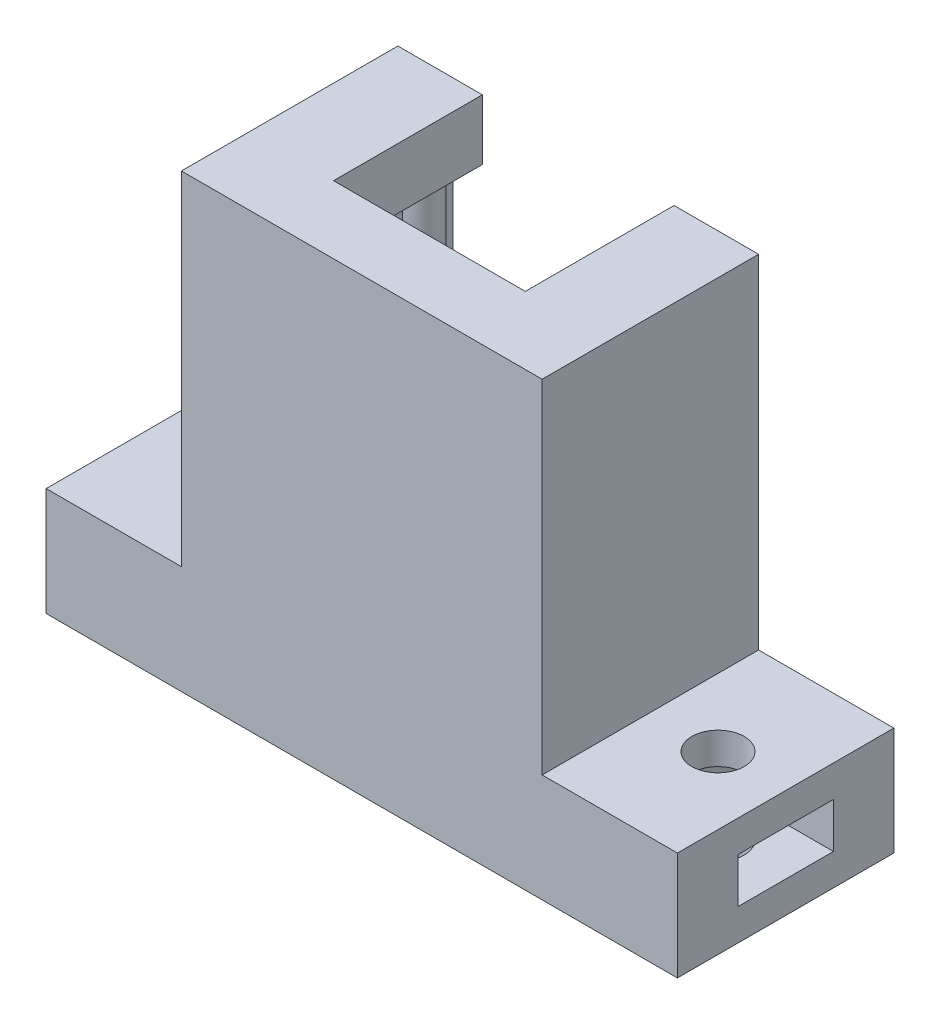
SolidWorks part; units mm, degrees
ref_plane "Front Plane" through (0, 0, 0) normal (0, 0, 1) x (1, 0, 0)
ref_plane "Top Plane" through (0, 0, 0) normal (0, 1, 0) x (1, 0, 0)
ref_plane "Right Plane" through (0, 0, 0) normal (1, 0, 0) x (0, 0, -1)
sketch "Sketch1" plane through (0, 0, 0) normal (0, 1, 0) x (1, 0, 0)
  line L1 (-17.5, -6) -> (17.5, -6)
  line L2 (-17.5, -6) -> (-17.5, 6)
  line L3 (-17.5, 6) -> (17.5, 6)
  line L4 (17.5, -6) -> (17.5, 6)
  line L5 (-17.5, -6) -> (17.5, 6) construction
  line L6 (-17.5, 6) -> (17.5, -6) construction
  point P0 (0, 0)
  dimension "D1" = 35
  dimension "D2" = 12
extrude "Boss-Extrude1" add sketch "Sketch1" along normal blind 6
sketch "Sketch2" plane through (0, 0, 0) normal (0, 1, 0) x (1, 0, 0)
  line L0 (17.5, 6) -> (-17.5, 6) construction
  line L1 (-10, -6) -> (10, -6)
  line L2 (-10, -6) -> (-10, 6)
  line L3 (-10, 6) -> (10, 6)
  line L4 (10, -6) -> (10, 6)
  line L5 (-10, -6) -> (10, 6) construction
  line L6 (-10, 6) -> (10, -6) construction
  point P0 (0, 0)
  point P5 (0, 0)
  dimension "D1" = 20
extrude "Boss-Extrude2" add sketch "Sketch2" along normal blind 25
sketch "Sketch3" plane through (0, 0, 0) normal (0, 1, 0) x (1, 0, 0)
  line L4 (-6.68, 2.615) -> (-6.68, -2.615)
  line L5 (-5.68, -3.615) -> (5.68, -3.615)
  line L6 (6.68, -2.615) -> (6.68, 2.615)
  line L7 (5.68, 3.615) -> (-5.68, 3.615)
  line L8 (-6.68, 2.615) -> (-6.68, -2.615)
  line L9 (-5.68, -3.615) -> (5.68, -3.615)
  line L10 (6.68, -2.615) -> (6.68, 2.615)
  line L11 (5.68, 3.615) -> (-5.68, 3.615)
  arc A4 (-6.68, -2.615) -> (-5.68, -3.615) centre (-5.68, -2.615) ccw
  arc A5 (5.68, -3.615) -> (6.68, -2.615) centre (5.68, -2.615) ccw
  arc A6 (6.68, 2.615) -> (5.68, 3.615) centre (5.68, 2.615) ccw
  arc A7 (-5.68, 3.615) -> (-6.68, 2.615) centre (-5.68, 2.615) ccw
  arc A8 (-6.68, -2.615) -> (-5.68, -3.615) centre (-5.68, -2.615) ccw
  arc A9 (5.68, -3.615) -> (6.68, -2.615) centre (5.68, -2.615) ccw
  arc A10 (6.68, 2.615) -> (5.68, 3.615) centre (5.68, 2.615) ccw
  arc A11 (-5.68, 3.615) -> (-6.68, 2.615) centre (-5.68, 2.615) ccw
  circle A36 centre (3.065, 0) radius 2.75 construction
  circle A37 centre (3.065, 0) radius 2.75
  circle A38 centre (-3.065, 0) radius 2.75 construction
  circle A39 centre (-3.065, 0) radius 2.75
  point P18 (0, 0)
  dimension "D1" = 0
sketch "Sketch5" plane through (0, 0, 0) normal (0, 1, 0) x (1, 0, 0)
  line L5 (6.93, 6) -> (6.93, -2.365)
  line L6 (17.5, 6) -> (-17.5, 6) construction
  line L7 (5.68, -3.615) -> (-5.68, -3.615)
  line L8 (-6.93, -2.365) -> (-6.93, 6)
  line L13 (-6.93, 6) -> (6.93, 6)
  line L14 (-6.68, 2.615) -> (-6.93, 2.615) construction
  line L15 (6.68, 2.615) -> (6.93, 2.615) construction
  arc A3 (6.93, -2.365) -> (5.68, -3.615) centre (5.68, -2.365) cw
  arc A4 (-5.68, -3.615) -> (-6.93, -2.365) centre (-5.68, -2.365) cw
  dimension "D1" = 0.25
extrude "Cut-Extrude1" cut sketch "Sketch5" along normal up to surface (21.65 mm away) up to face at (0, 0, 0)
sketch "Sketch6" plane through (0, 25, 0) normal (0, 1, 0) x (1, 0, 0)
  line L0 (-5.315, 6) -> (-5.315, -2.25)
  line L1 (10, 6) -> (-10, 6) construction
  line L2 (-5.315, -2.25) -> (5.315, -2.25)
  line L3 (5.315, -2.25) -> (5.315, 6)
  line L4 (5.315, 6) -> (-5.315, 6)
  line L6 (-6.68, 2.615) -> (-5.315, 2.615) construction
  line L7 (5.315, -2.25) -> (5.315, -3.615) construction
  line L8 (-5.68, -3.615) -> (5.68, -3.615) construction
  line L9 (5.315, -2.25) -> (6.68, -2.25) construction
  line L10 (6.68, -2.615) -> (6.68, 2.615) construction
  line L11 (-4.815, 0) -> (-5.315, 0) construction
  circle A4 centre (-3.065, 0) radius 1.75 construction
  dimension "D1" = 0.5
  dimension "D2" = 3.5
extrude "Cut-Extrude2" cut sketch "Sketch6" against normal up to surface (3.35 mm away) up to face at (0, 21.65, 0.0796)
sketch "Sketch8" plane through (0, 0, 0) normal (0, -1, 0) x (1, 0, 0)
  line L0 (-6.93, -6) -> (-6.93, 2.365) construction
  line L1 (6.93, 2.365) -> (6.93, -6) construction
  line L2 (-6.68, -2.615) -> (-6.68, 2.615) construction
  circle A0 centre (-6.93, -4.1762) radius 1
  circle A1 centre (6.93, -4.1762) radius 1
  arc A2 (-6.68, -2.615) -> (-5.68, -3.615) centre (-5.68, -2.615) ccw construction
  arc A3 (5.68, -3.615) -> (6.68, -2.615) centre (5.68, -2.615) ccw construction
  point P14 (-5.93, -4.1762)
  dimension "D1" = 0.75
extrude "Boss-Extrude3" add sketch "Sketch8" against normal up to surface (21.65 mm away) up to face at (0, 21.65, -0.7022)
sketch "Sketch9" plane through (0, 7.21, 0) normal (0, -1, 0) x (1, 0, 0)
  line L1 (6.93, -5.425) -> (-6.93, -5.425)
  line L2 (6.93, -5.425) -> (6.93, 5.425)
  line L3 (6.93, 5.425) -> (-6.93, 5.425)
  line L4 (-6.93, -5.425) -> (-6.93, 5.425)
  line L7 (2.36, 4.925) -> (-2.36, 4.925) construction
  line L8 (2.36, 4.925) -> (-2.36, 4.925) construction
  line L9 (-5.37, -4.925) -> (-4.56, -4.925) construction
  line L10 (-5.37, -4.925) -> (-4.56, -4.925) construction
  line L11 (6.93, 2.365) -> (6.93, -3.1762) construction
  line L12 (-6.93, -3.1762) -> (-6.93, 2.365) construction
  dimension "D1" = 0.5
  dimension "D2" = 0.5
extrude "Cut-Extrude3" cut sketch "Sketch9" against normal blind 1.5 and the other way blind 0.5
ref_plane "Plane1" through (0, 3, 0) normal (0, -1, 0) x (-1, 0, 0)
sketch "Sketch10" plane through (0, 3, 0) normal (0, -1, 0) x (-1, 0, 0)
  line L0 (10, 6) -> (17.5, -6) construction
  line L1 (-15.28, -2.65) -> (-17.5, -2.65)
  line L2 (17.5, 6) -> (17.5, -6) construction
  line L3 (16.81, 0) -> (15.28, 2.65) construction
  line L4 (15.28, 2.65) -> (12.22, 2.65)
  line L5 (12.22, 2.65) -> (10.69, 0)
  line L6 (10.69, 0) -> (12.22, -2.65)
  line L7 (12.22, -2.65) -> (15.28, -2.65)
  line L8 (15.28, -2.65) -> (16.81, 0) construction
  line L9 (15.28, 2.65) -> (17.5, 2.65)
  line L11 (15.28, -2.65) -> (17.5, -2.65)
  line L12 (17.5, 2.65) -> (17.5, -2.65)
  line L13 (0, 0) -> (0, 8.3282) construction
  line L14 (-12.22, -2.65) -> (-15.28, -2.65)
  line L15 (-10.69, 0) -> (-12.22, -2.65)
  line L16 (-12.22, 2.65) -> (-10.69, 0)
  line L17 (-15.28, 2.65) -> (-12.22, 2.65)
  line L18 (-15.28, 2.65) -> (-17.5, 2.65)
  line L19 (-17.5, 2.65) -> (-17.5, -2.65)
  circle A0 centre (13.75, 0) radius 2.65 construction
  circle A1 centre (13.75, 0) radius 2.5 construction
  dimension "D1" = 5
  dimension "D2" = 0.15
extrude "Cut-Extrude4" cut sketch "Sketch10" against normal mid plane 2.5
hole_wizard "M2.5 Clearance Hole1" positions "Sketch13" profile "Sketch12" hole size "M2.5" standard "ANSI Metric" end condition through all
sketch "Sketch13" plane through (0, 0, 0) normal (0, -1, 0) x (-1, 0, 0)
  line L0 (-13.75, 0) -> (13.75, 0) construction
  point P0 (13.75, 0)
  point P3 (-13.75, 0)
sketch "Sketch12" plane through (-13.75, 0, 0) normal (1, 0, 0) x (0, 0, -1)
  line L0 (0, 0) -> (0, 25)
  line L1 (0, 25) -> (1.45, 25)
  line L2 (1.45, 25) -> (1.45, 0)
  line L5 (1.45, 0) -> (0, 0)
  line L11 (0, -6.35) -> (0, 107.95) construction
  dimension "Thru Hole Dia." = 2.9
  dimension "Thru Hole Depth" = 25
